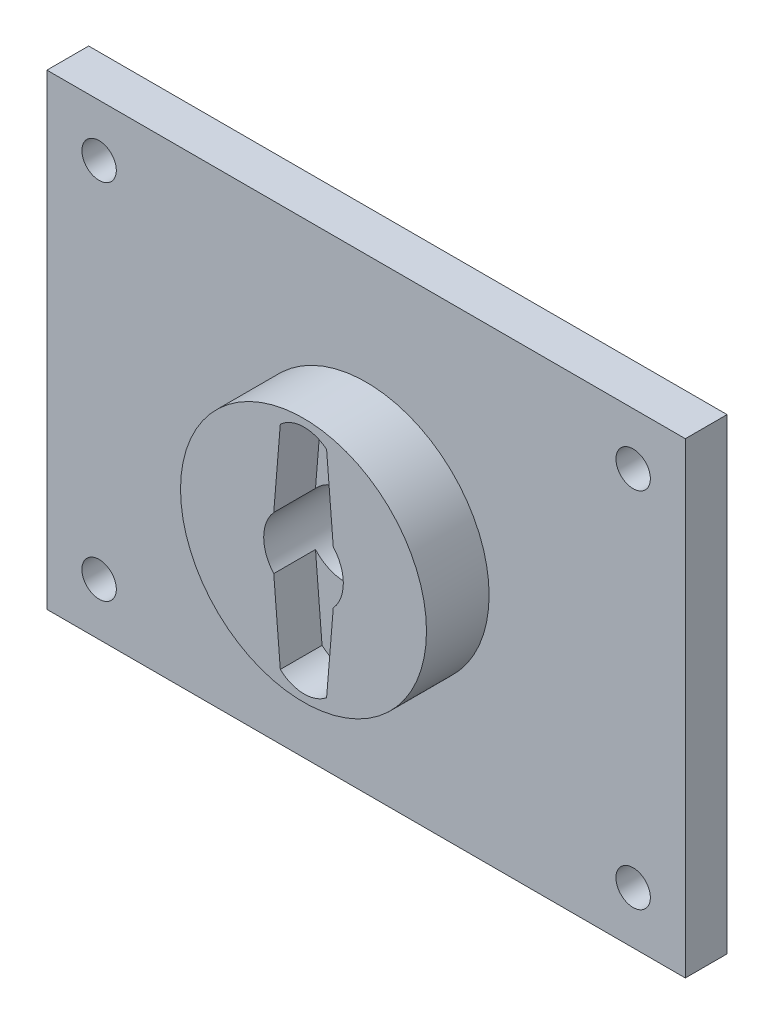
SolidWorks part; units mm, degrees
material "ABS"
ref_plane "Plan de face" through (0, 0, 0) normal (0, 0, 1) x (1, 0, 0)
ref_plane "Plan de dessus" through (0, 0, 0) normal (0, 1, 0) x (1, 0, 0)
ref_plane "Plan de droite" through (0, 0, 0) normal (1, 0, 0) x (0, 0, -1)
sketch "Esquisse1" plane through (0, 0, 0) normal (0, 0, 1) x (1, 0, 0)
  line L0 (30.5845, -22.376) -> (-30.5845, -22.376)
  line L1 (20.5845, 12.376) -> (-20.5845, 12.376) construction
  line L2 (20.5845, 12.376) -> (20.5845, -12.376) construction
  line L3 (20.5845, -12.376) -> (-20.5845, -12.376) construction
  line L4 (-20.5845, 12.376) -> (-20.5845, -12.376) construction
  line L5 (-30.5845, 22.376) -> (-30.5845, -22.376)
  line L6 (30.5845, 22.376) -> (-30.5845, 22.376)
  line L7 (30.5845, 22.376) -> (30.5845, -22.376)
  circle A0 centre (0, 0) radius 3.8155
extrude "Boss.-Extru.2" add sketch "Esquisse1" along normal blind 4 separate body
sketch "Esquisse2" plane through (0, 0, 0) normal (0, 0, 1) x (1, 0, 0)
  circle A0 centre (0, 0) radius 11.7835
extrude "Boss.-Extru.4" add sketch "Esquisse2" along normal blind 6 from offset 4
sketch "Esquisse4" plane through (0, 0, 10) normal (0, 0, 1) x (1, 0, 0)
  line L2 (2.8702, 2.3029) -> (2.2123, 10.3068)
  line L3 (-2.223, 10.1764) -> (-2.8702, 2.3029)
  line L4 (0, 0) -> (1.9304, 0) construction
  line L5 (-2.223, -10.1764) -> (-2.8702, -2.3029)
  line L6 (2.8702, -2.3029) -> (2.2123, -10.3068)
  arc A0 (-2.8702, 2.3029) -> (-2.8702, -2.3029) centre (0, 0) ccw
  arc A1 (-2.223, 10.1764) -> (2.2123, 10.3068) centre (0.0696, 7.6914) cw
  arc A2 (-2.223, -10.1764) -> (2.2123, -10.3068) centre (0.0696, -7.6914) ccw
  arc A3 (2.8702, -2.3029) -> (2.8702, 2.3029) centre (0, 0) ccw
extrude "Enlèv. mat.-Extru.1" cut sketch "Esquisse4" against normal blind 4
extrude "Enlèv. mat.-Extru.3" cut sketch "Esquisse1<2>" along normal through all contours A0 region at (0, 0, 0)
sketch "Esquisse1<2>" plane through (0, 0, 0) normal (0, 0, 1) x (1, 0, 0) same geometry as "Esquisse1"
sketch "Sketch1" plane through (0, 0, 4) normal (0, 0, 1) x (1, 0, 0)
  line L0 (0, -1000) -> (0, 49000) construction
  line L1 (-1000, 0) -> (49000, 0) construction
  line L2 (30.5845, 22.376) -> (-30.5845, 22.376) construction
  line L3 (-30.5845, 22.376) -> (-30.5845, -22.376) construction
  circle A0 centre (-25.5845, 17.376) radius 1.65
  circle A1 centre (25.5845, 17.376) radius 1.65
  circle A2 centre (25.5845, -17.376) radius 1.65
  circle A3 centre (-25.5845, -17.376) radius 1.65
  dimension "D1" = 3.3
  dimension "D2" = 5
  dimension "D3" = 5
extrude "Cut-Extrude1" cut sketch "Sketch1" against normal blind 10
